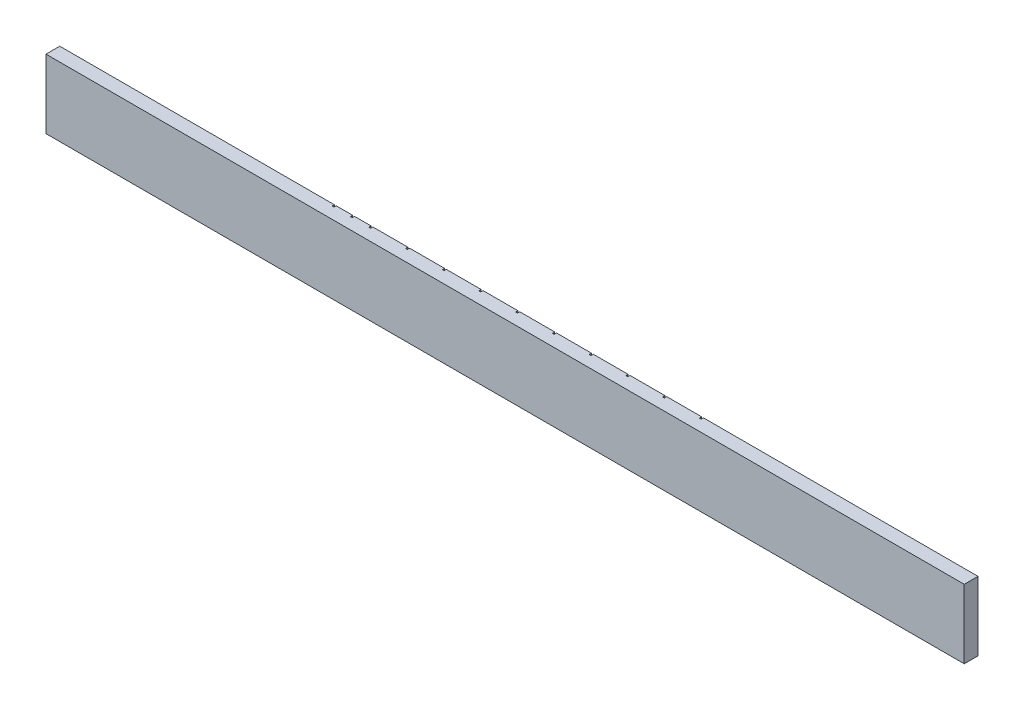
SolidWorks part; units mm, degrees
material "Brass"
ref_plane "Front Plane" through (0, 0, 0) normal (0, 0, 1) x (1, 0, 0)
ref_plane "Top Plane" through (0, 0, 0) normal (0, 1, 0) x (1, 0, 0)
ref_plane "Right Plane" through (0, 0, 0) normal (1, 0, 0) x (0, 0, -1)
sketch "Sketch1" plane through (0, 0, 0) normal (0, 0, 1) x (1, 0, 0)
  line L0 (0, 0) -> (200, 0)
  line L1 (200, 0) -> (200, 15)
  line L2 (200, 15) -> (0, 15)
  line L3 (0, 15) -> (0, 0)
  dimension "D1" = 200
  dimension "D2" = 15
extrude "Boss-Extrude1" add sketch "Sketch1" along normal blind 3
sketch "Sketch2" plane through (0, 0, 0) normal (0, 0, 1) x (1, 0, 0)
  line L0 (59.8, 9) -> (60.2, 9)
  line L1 (60.2, 9) -> (60.2, 16)
  line L2 (60.2, 16) -> (59.8, 16)
  line L3 (59.8, 16) -> (59.8, 9)
  dimension "D1" = 0.4
  dimension "D2" = 7
  dimension "D3" = 59.8
  dimension "D4" = 9
extrude "Cut-Extrude2" cut sketch "Sketch2" against normal blind 0.5 and the other way blind 0.5
pattern_linear "LPattern1" count 11 spacing 8 along (1, 0, 0) of "Cut-Extrude2"
sketch "Sketch3" plane through (0, 0, 0) normal (0, 0, 1) x (1, 0, 0)
  line L0 (63.8, 8) -> (64.2, 8)
  line L1 (64.2, 8) -> (64.2, 16)
  line L2 (64.2, 16) -> (63.8, 16)
  line L3 (63.8, 16) -> (63.8, 8)
  dimension "D1" = 0.4
  dimension "D2" = 8
  dimension "D3" = 63.8
  dimension "D4" = 8
extrude "Cut-Extrude4" cut sketch "Sketch3" against normal blind 0.5 and the other way blind 0.5
